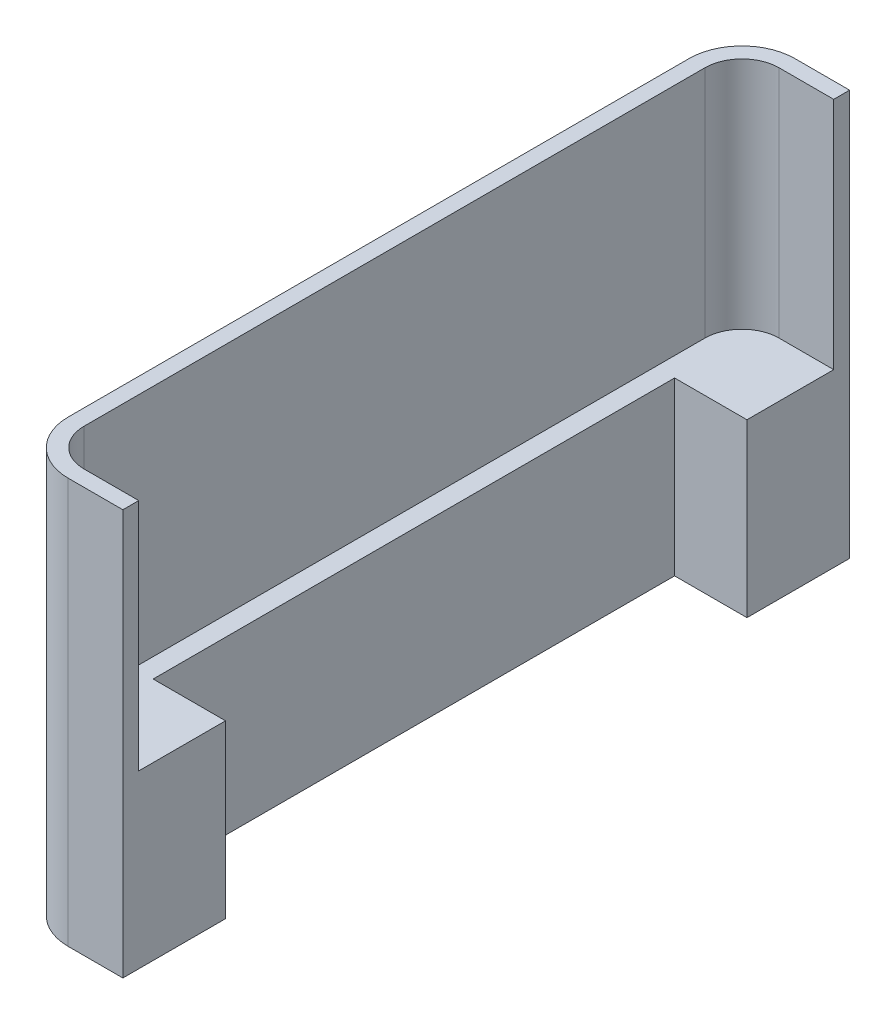
SolidWorks part; units mm, degrees
ref_plane "Front Plane" through (0, 0, 0) normal (0, 0, 1) x (1, 0, 0)
ref_plane "Top Plane" through (0, 0, 0) normal (0, 1, 0) x (1, 0, 0)
ref_plane "Right Plane" through (0, 0, 0) normal (1, 0, 0) x (0, 0, -1)
sketch "Sketch1" plane through (0, 1.61, 0) normal (0, 1, 0) x (1, 0, 0)
  line L0 (-46.865, 18.735) -> (-46.865, -6.665) construction
  line L1 (-44.325, 18.735) -> (-46.865, 18.735) construction
  line L2 (-45.22, 17.84) -> (-45.97, 17.84) construction
  line L3 (-45.97, -5.77) -> (-45.97, 17.84) construction
  line L4 (-46.865, 18.735) -> (-46.865, -6.665)
  line L5 (-44.325, 18.735) -> (-46.865, 18.735)
  line L6 (-45.22, 17.84) -> (-45.97, 17.84)
  line L7 (-45.97, -5.77) -> (-45.97, 17.84)
sketch "Sketch2" plane through (0, 1.61, 0) normal (0, 1, 0) x (1, 0, 0)
  line L0 (-48.135, 6.035) -> (-46.865, 6.035) construction
  line L1 (-48.135, -11.115) -> (-43.055, -11.115)
  line L2 (-48.135, -11.115) -> (-48.135, 23.185)
  line L3 (-48.135, 23.185) -> (-43.055, 23.185)
  line L4 (-43.055, -11.115) -> (-43.055, 23.185)
  line L5 (-46.865, 18.735) -> (-46.865, -6.665) construction
  line L6 (-45.595, 18.735) -> (-45.595, 23.185) construction
  line L7 (-44.325, 18.735) -> (-46.865, 18.735) construction
  dimension "D1" = 4.45
  dimension "D2" = 1.27
extrude "Boss-Extrude1" add sketch "Sketch2" along normal up to surface (19.1389 mm away)
fillet "Fillet1" radius 2.5 2 edges at (-48.135, 11.1795, 11.115) (-48.135, 11.1795, -23.185)
ref_plane "Plane1" through (0, 9.7, 0) normal (0, -1, 0) x (-1, 0, 0)
sketch "Sketch3" plane through (0, 9.7, 0) normal (0, -1, 0) x (-1, 0, 0)
  line L0 (45.595, 17.84) -> (45.595, 18.34) construction
  line L1 (45.22, 17.84) -> (45.97, 17.84) construction
  line L2 (43.055, -6.27) -> (46.47, -6.27)
  line L3 (43.055, -6.27) -> (43.055, 18.34)
  line L4 (43.055, 18.34) -> (46.47, 18.34)
  line L5 (46.47, -6.27) -> (46.47, 18.34)
  line L6 (45.97, -5.77) -> (45.97, 17.84) construction
  line L7 (45.22, 17.84) -> (45.97, 17.84) construction
  line L8 (45.97, -5.77) -> (45.97, 17.84) construction
  line L9 (46.47, 6.035) -> (45.97, 6.035) construction
  line L10 (43.055, -11.115) -> (43.055, 23.185) construction
  dimension "D1" = 0.5
  dimension "D2" = 0.5
extrude "Cut-Extrude1" cut sketch "Sketch3" along normal through all
sketch "Sketch4" plane through (0, 20.7489, 0) normal (0, 1, 0) x (1, 0, 0)
  line L9 (-43.055, -10.365) -> (-43.055, 22.435)
  line L12 (-43.055, 22.435) -> (-45.635, 22.435)
  line L13 (-47.385, 20.685) -> (-47.385, -8.615)
  line L14 (-45.635, -10.365) -> (-43.055, -10.365)
  line L15 (-43.055, 22.435) -> (-45.635, 22.435)
  line L16 (-47.385, 20.685) -> (-47.385, -8.615)
  line L17 (-45.635, -10.365) -> (-43.055, -10.365)
  arc A8 (-45.635, 22.435) -> (-47.385, 20.685) centre (-45.635, 20.685) ccw
  arc A9 (-47.385, -8.615) -> (-45.635, -10.365) centre (-45.635, -8.615) ccw
  arc A10 (-45.635, 22.435) -> (-47.385, 20.685) centre (-45.635, 20.685) ccw
  arc A11 (-47.385, -8.615) -> (-45.635, -10.365) centre (-45.635, -8.615) ccw
  dimension "D1" = 0.75
extrude "Cut-Extrude2" cut sketch "Sketch4" against normal up to surface (11.0489 mm away) up to face at (-44.7625, 9.7, -6.035)
